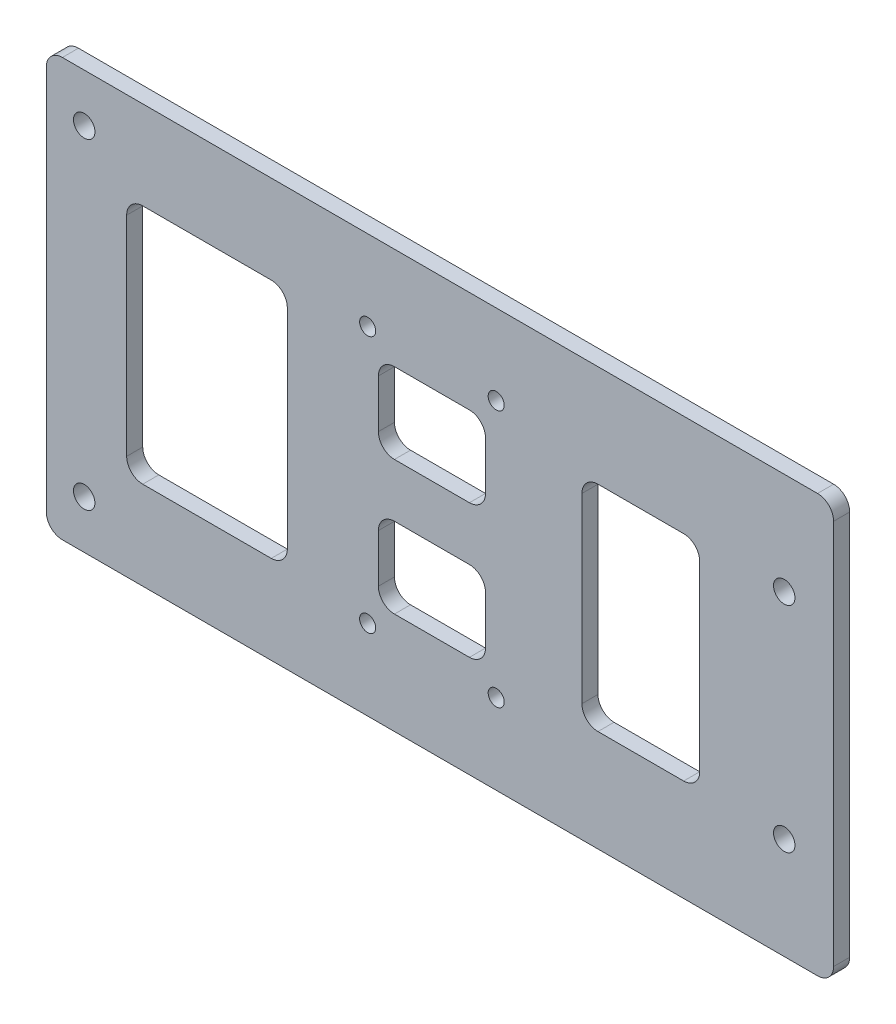
SolidWorks part; units mm, degrees
material "Caoba"
ref_plane "Alzado" through (0, 0, 0) normal (0, 0, 1) x (1, 0, 0)
ref_plane "Planta" through (0, 0, 0) normal (0, 1, 0) x (1, 0, 0)
ref_plane "Vista lateral" through (0, 0, 0) normal (1, 0, 0) x (0, 0, -1)
sketch "Croquis1" plane through (0, 0, 0) normal (0, 0, 1) x (1, 0, 0)
  circle A0 centre (0, 0) radius 100
  dimension "D1" = 200
extrude "Saliente-Extruir1" add sketch "Croquis1" along normal blind 3
sketch "Croquis3" plane through (0, 0, 3) normal (0, 0, 1) x (1, 0, 0)
  line L0 (0, 0) -> (190, 0) construction
  circle A0 centre (190, 0) radius 120
  dimension "D1" = 240
  dimension "D2" = 190
extrude "Cortar-Extruir1" cut sketch "Croquis3" against normal blind 3
sketch "Croquis5" plane through (0, 0, 3) normal (0, 0, 1) x (1, 0, 0)
  line L0 (0, -100) -> (0, 100) construction
  line L1 (-100, 0) -> (70, 0) construction
  line L2 (0, 0) -> (-70.7107, -70.7107) construction
  line L3 (-70.7107, -70.7107) -> (70.7107, 70.7107) construction
  line L4 (0, 0) -> (-70.7107, 70.7107) construction
  line L5 (-70.7107, 70.7107) -> (70.7107, -70.7107) construction
  line L6 (-70.7107, -70.7107) -> (-58.3363, -83.085) construction
  line L9 (-58.3363, -83.085) -> (-83.085, -58.3363)
  line L11 (-83.085, -58.3363) -> (-65.4074, -40.6586)
  line L12 (-65.4074, -40.6586) -> (-40.6586, -65.4074)
  line L13 (-40.6586, -65.4074) -> (-58.3363, -83.085)
  line L14 (-70.7107, 70.7107) -> (-83.085, 58.3363) construction
  line L15 (-83.085, 58.3363) -> (-100, 0) construction
  line L17 (-83.085, 58.3363) -> (-58.3363, 83.085)
  line L18 (-58.3363, 83.085) -> (-40.6586, 65.4074)
  line L19 (-40.6586, 65.4074) -> (-65.4074, 40.6586)
  line L20 (-65.4074, 40.6586) -> (-83.085, 58.3363)
  line L22 (70.7107, -70.7107) -> (58.3363, -83.085) construction
  line L23 (58.3363, -83.085) -> (0, -100) construction
  line L24 (58.3363, -83.085) -> (83.085, -58.3363)
  line L25 (83.085, -58.3363) -> (65.4074, -40.6586)
  line L26 (65.4074, -40.6586) -> (40.6586, -65.4074)
  line L27 (40.6586, -65.4074) -> (58.3363, -83.085)
  line L28 (70.7107, 70.7107) -> (58.3363, 83.085) construction
  line L29 (58.3363, 83.085) -> (0, 100) construction
  line L30 (58.3363, 83.085) -> (83.085, 58.3363)
  line L31 (83.085, 58.3363) -> (65.4074, 40.6586)
  line L32 (65.4074, 40.6586) -> (40.6586, 65.4074)
  line L33 (40.6586, 65.4074) -> (58.3363, 83.085)
  arc A0 (83.4211, 55.1446) -> (83.4211, -55.1446) centre (0, 0) ccw construction
  arc A1 (83.4211, 55.1446) -> (83.4211, -55.1446) centre (190, 0) ccw construction
  point P36 (0, 0)
  dimension "D2" = 17.5
  dimension "D3" = 25
  dimension "D4" = 35
  dimension "D5" = 25
  dimension "D6" = 35
  dimension "D8" = 25
  dimension "D9" = 17.5
  dimension "D7" = 35
  dimension "D10" = 90
  dimension "D11" = 17.5
  dimension "D12" = 17.5
  dimension "D13" = 35
  dimension "D14" = 25
  dimension "D15" = 134.3503
  dimension "D16" = 100
extrude "Cortar-Extruir6" cut sketch "Croquis5" against normal blind 10
sketch "Croquis12" plane through (0, 0, 3) normal (0, 0, 1) x (1, 0, 0)
  line L0 (-53.033, -53.033) -> (-39.9421, -50.0116) construction
  line L1 (-40.6586, -65.4074) -> (-65.4074, -40.6586) construction
  line L2 (-39.9421, -50.0116) -> (-36.8049, -63.6043) construction
  line L3 (-36.8049, -63.6043) -> (-63.6043, -36.8049) construction
  line L4 (-63.6043, -36.8049) -> (-47.6661, -20.8667) construction
  line L6 (53.033, -53.033) -> (-53.033, 53.033) construction
  line L7 (65.4074, -40.6586) -> (40.6586, -65.4074) construction
  line L8 (-65.4074, 40.6586) -> (-40.6586, 65.4074) construction
  line L9 (36.8049, 63.6043) -> (20.8667, 47.6661) construction
  line L10 (63.6043, 36.8049) -> (36.8049, 63.6043) construction
  line L11 (50.0116, 39.9421) -> (63.6043, 36.8049) construction
  line L12 (53.033, 53.033) -> (50.0116, 39.9421) construction
  line L14 (53.033, -53.033) -> (50.2046, -50.2046) construction
  line L15 (50.2046, -50.2046) -> (36.8049, -63.6043) construction
  line L16 (36.8049, -63.6043) -> (63.6043, -36.8049) construction
  line L17 (63.6043, -36.8049) -> (47.6661, -20.8667) construction
  line L19 (-53.033, -53.033) -> (53.033, 53.033) construction
  line L20 (-36.8049, 63.6043) -> (-20.8667, 47.6661) construction
  line L21 (-63.6043, 36.8049) -> (-36.8049, 63.6043) construction
  line L22 (-50.2046, 50.2046) -> (-63.6043, 36.8049) construction
  line L23 (-53.033, 53.033) -> (-50.2046, 50.2046) construction
  circle A0 centre (-63.6043, -36.8049) radius 1.5
  circle A1 centre (-36.8049, -63.6043) radius 1.5
  circle A2 centre (-47.6661, -20.8667) radius 1.5
  circle A3 centre (-20.8667, -47.6661) radius 1.5
  circle A5 centre (47.6661, 20.8667) radius 1.5
  circle A6 centre (20.8667, 47.6661) radius 1.5
  circle A7 centre (63.6043, 36.8049) radius 1.5
  circle A8 centre (36.8049, 63.6043) radius 1.5
  circle A10 centre (20.8667, -47.6661) radius 1.5
  circle A11 centre (47.6661, -20.8667) radius 1.5
  circle A12 centre (63.6043, -36.8049) radius 1.5
  circle A13 centre (36.8049, -63.6043) radius 1.5
  circle A15 centre (-63.6043, 36.8049) radius 1.5
  circle A16 centre (-36.8049, 63.6043) radius 1.5
  circle A17 centre (-20.8667, 47.6661) radius 1.5
  circle A18 centre (-47.6661, 20.8667) radius 1.5
  dimension "D2" = 3
  dimension "D3" = 3
  dimension "D4" = 4
  dimension "D5" = 4
  dimension "D6" = 3
  dimension "D7" = 3
  dimension "D8" = 37.9
  dimension "D9" = 22.54
  dimension "D10" = 22.54
  dimension "D11" = 37.9
  dimension "D12" = 18.95
  dimension "D13" = 18.95
  dimension "D14" = 3
  dimension "D15" = 3
  dimension "D16" = 3
  dimension "D17" = 3
  dimension "D18" = 37.9
  dimension "D19" = 22.54
  dimension "D20" = 22.54
  dimension "D21" = 37.9
  dimension "D22" = 4
  dimension "D1" = 13.95
extrude "Cortar-Extruir7" cut sketch "Croquis12" against normal through all
sketch "Croquis9" plane through (0, 0, 3) normal (0, 0, 1) x (1, 0, 0)
  line L0 (0, 0) -> (-100, 0) construction
  line L5 (0, 100) -> (0, -100) construction
  line L6 (20, 5) -> (29, 5)
  line L7 (20, 5) -> (20, -5)
  line L8 (20, -5) -> (29, -5)
  line L9 (29, 5) -> (29, -5)
  line L10 (-5, -49) -> (5, -49)
  line L11 (-49, 5) -> (-58, 5)
  line L12 (-49, 5) -> (-49, -5)
  line L13 (-49, -5) -> (-58, -5)
  line L14 (-58, 5) -> (-58, -5)
  line L15 (-5, 58) -> (5, 58)
  line L16 (-5, 58) -> (-5, 49)
  line L17 (-5, 49) -> (5, 49)
  line L18 (5, 58) -> (5, 49)
  line L19 (5, -58) -> (5, -49)
  line L20 (-5, -58) -> (5, -58)
  line L21 (-5, -58) -> (-5, -49)
  line L22 (0, 0) -> (70, 0) construction
  line L24 (-52.061, -4) -> (-52.0837, -4) construction
  arc A6 (-81.9939, 57.2451) -> (-81.9939, -57.2451) centre (0, 0) ccw construction
  arc A7 (83.4211, 55.1446) -> (83.4211, -55.1446) centre (190, 0) ccw construction
  dimension "D7" = 49
  dimension "D8" = 49
  dimension "D9" = 20
  dimension "D10" = 49
  dimension "D28" = 5
  dimension "D37" = 5
  dimension "D62" = 9
  dimension "D32" = 10
  dimension "D50" = 5
  dimension "D17" = 9
  dimension "D18" = 10
  dimension "D33" = 5
  dimension "D47" = 10
  dimension "D48" = 9
  dimension "D66" = 9
  dimension "D67" = 10
extrude "Cortar-Extruir5" cut sketch "Croquis9" against normal blind 10
sketch "Croquis13" plane through (0, 0, 3) normal (0, 0, 1) x (1, 0, 0)
  line L0 (0, 100) -> (0, -100) construction
  line L1 (-100, 0) -> (70, 0) construction
  line L2 (-70.7107, 70.7107) -> (70.7107, -70.7107) construction
  line L3 (-70.7093, -70.7093) -> (70.712, 70.712) construction
  line L4 (-70.7107, 70.7107) -> (-70.7093, -70.7093) construction
  line L5 (-70.7093, -70.7093) -> (70.7107, -70.7107) construction
  line L6 (70.7107, -70.7107) -> (70.712, 70.712) construction
  line L7 (70.712, 70.712) -> (-70.7107, 70.7107) construction
  line L9 (-37, 20) -> (8, 20)
  line L10 (-37, 20) -> (-37, -18)
  line L11 (-37, -18) -> (8, -18)
  line L12 (8, 20) -> (8, -18)
  arc A0 (57.2451, 81.9939) -> (-57.2451, 81.9939) centre (0, 0) ccw construction
  arc A1 (-57.2451, -81.9939) -> (57.2451, -81.9939) centre (0, 0) ccw construction
  arc A2 (-81.9939, 57.2451) -> (-81.9939, -57.2451) centre (0, 0) ccw construction
  arc A3 (83.4211, 55.1446) -> (83.4211, -55.1446) centre (190, 0) ccw construction
  circle A4 centre (-70.7103, 30) radius 2
  circle A5 centre (-70.7097, -30) radius 2
  circle A8 centre (0, -93.47) radius 1.5
  circle A9 centre (0, 93.47) radius 1.5
  circle A10 centre (60, -20) radius 2
  circle A11 centre (60, 20) radius 2
  point P37 (-15, 0)
  dimension "D9" = 4
  dimension "D10" = 4
  dimension "D11" = 30
  dimension "D12" = 30
  dimension "D13" = 4
  dimension "D14" = 4
  dimension "D15" = 60
  dimension "D16" = 60
  dimension "D17" = 3
  dimension "D18" = 93.47
  dimension "D19" = 93.47
  dimension "D20" = 3
  dimension "D25" = 20
  dimension "D26" = 20
  dimension "D1" = 45
  dimension "D2" = 200
  dimension "D3" = 0
  dimension "D4" = 200
  dimension "D5" = 45
  dimension "D6" = 0
  dimension "D7" = 141.42
  dimension "D8" = 141.42
  dimension "D21" = 45
  dimension "D22" = 38
  dimension "D23" = 18
  dimension "D24" = 37
extrude "Cortar-Extruir8" cut sketch "Croquis13" against normal through all
fillet "Redondeo2" radius 3 20 edges at (-81.9939, 57.2451, 1.5) (-65.4074, 40.6586, 1.5) (-40.6586, 65.4074, 1.5) (-57.2451, 81.9939, 1.5) (65.4074, 40.6586, 1.5) (40.6586, 65.4074, 1.5) (57.2451, 81.9939, 1.5) (81.9939, 57.2451, 1.5) (65.4074, -40.6586, 1.5) (40.6586, -65.4074, 1.5) (81.9939, -57.2451, 1.5) (57.2451, -81.9939, 1.5) (-65.4074, -40.6586, 1.5) (-81.9939, -57.2451, 1.5) (-57.2451, -81.9939, 1.5) (-40.6586, -65.4074, 1.5) (8, -18, 1.5) (8, 20, 1.5) (-37, -18, 1.5) (-37, 20, 1.5)
fillet "Redondeo3" radius 3 2 edges at (83.4211, -55.1446, 1.5) (83.4211, 55.1446, 1.5)
sketch "Croquis14" plane through (0, 0, 3) normal (0, 0, 1) x (1, 0, 0)
  line L0 (42.78, -67.5287) -> (54.6657, -79.4145) construction
  line L1 (0, 0) -> (75.1866, -75.1866) construction
  line L2 (0, 100) -> (0, -100) construction
  line L7 (-100, 0) -> (83.579, 0) construction
  line L8 (0, 0) -> (88.3883, 88.3883) construction
  line L9 (0, 0) -> (-88.3883, -88.3883) construction
  line L10 (0, 0) -> (-74.4604, 74.4604) construction
  circle A0 centre (38.8032, -75) radius 1.5
  circle A1 centre (-75, -38.8032) radius 1.5
  circle A2 centre (-38.7968, -75) radius 1.5
  circle A8 centre (-75, 38.7968) radius 1.5
  circle A9 centre (-38.8032, 75) radius 1.5
  circle A10 centre (38.7968, 75) radius 1.5
  arc A12 (54.1695, 84.0575) -> (-54.1695, 84.0575) centre (0, 0) ccw construction
  arc A13 (-54.1695, -84.0575) -> (54.1695, -84.0575) centre (0, 0) ccw construction
  arc A14 (-84.0575, 54.1695) -> (-84.0575, -54.1695) centre (0, 0) ccw construction
  circle A26 centre (75, 38.8032) radius 1.5 [skipped]
  circle A27 centre (75, -38.7968) radius 1.5 [skipped]
  point P23 (-5.3984, -2.1885)
  point P24 (0, 0)
  dimension "D1" = 3
  dimension "D2" = 8.095
  dimension "D3" = 75
  dimension "D4" = 3
  dimension "D5" = 75
  dimension "D7" = 4
  dimension "D8" = 38.7968
  dimension "D9" = 75
  dimension "D24" = 77.6
  dimension "D6" = 125
  dimension "D19" = 125
  dimension "D20" = 45
  dimension "D21" = 45
  dimension "D22" = 45
  dimension "D23" = 45
extrude "Cortar-Extruir9" cut sketch "Croquis14" against normal through all
sketch "Croquis15" plane through (0, 0, 0) normal (0, 0, -1) x (-1, 0, 0)
  line L0 (0, 100) -> (0, -100) construction
  line L1 (-70, 0) -> (100, 0) construction
  circle A0 centre (16.19, 41.3081) radius 1.5
  circle A1 centre (16.19, -41.3181) radius 1.5
  arc A2 (54.1695, 84.0575) -> (-54.1695, 84.0575) centre (0, 0) ccw construction
  arc A3 (-54.1695, -84.0575) -> (54.1695, -84.0575) centre (0, 0) ccw construction
  arc A4 (-79.3447, -46.4262) -> (-79.3447, 46.4262) centre (-190, 0) ccw construction
  arc A5 (84.0575, -54.1695) -> (84.0575, 54.1695) centre (0, 0) ccw construction
  circle A6 centre (-16.705, -10.3179) radius 1.5
  dimension "D1" = 3
  dimension "D2" = 3
  dimension "D3" = 82.6262
  dimension "D4" = 16.19
  dimension "D5" = 41.3182
  dimension "D6" = 41.3081
  dimension "D7" = 3
  dimension "D8" = 51.626
  dimension "D9" = 32.895
extrude "Cortar-Extruir10" cut sketch "Croquis15" against normal blind 10
sketch "Croquis16" plane through (0, 0, 0) normal (0, 0, -1) x (-1, 0, 0)
  line L0 (-115, 0) -> (100, 0) construction
  line L1 (-115, 105) -> (100, 105)
  line L2 (-115, 105) -> (-115, 39)
  line L3 (-115, 39) -> (100, 39)
  line L4 (100, 105) -> (100, 39)
  line L5 (-115, -39) -> (100, -39)
  line L6 (100, -105) -> (100, -39)
  line L7 (-115, -105) -> (100, -105)
  line L8 (-115, -105) -> (-115, -39)
  line L9 (0, 100) -> (0, -100) construction
  arc A0 (84.0575, -54.1695) -> (84.0575, 54.1695) centre (0, 0) ccw construction
  arc A1 (54.1695, 84.0575) -> (-54.1695, 84.0575) centre (0, 0) ccw construction
  arc A2 (-54.1695, -84.0575) -> (54.1695, -84.0575) centre (0, 0) ccw construction
  dimension "D1" = 215
  dimension "D2" = 215
  dimension "D3" = 66
  dimension "D4" = 39
  dimension "D5" = 115
extrude "Cortar-Extruir11" cut sketch "Croquis16" against normal blind 10
sketch "Croquis17" plane through (0, 0, 0) normal (0, 0, -1) x (-1, 0, 0)
  line L5 (-76.5143, -39) -> (73.513, -39) construction
  line L6 (80, -34) -> (-70, -34)
  line L7 (80, -34) -> (80, -39)
  line L8 (80, -39) -> (-70, -39)
  line L9 (-70, -34) -> (-70, -39)
  line L10 (100, 0) -> (-70, 0) construction
  line L11 (80, 39) -> (-70, 39)
  line L12 (-70, 34) -> (-70, 39)
  line L13 (80, 34) -> (-70, 34)
  line L14 (80, 34) -> (80, 39)
  line L16 (87, 25) -> (-53, 25)
  line L17 (87, 25) -> (87, -25)
  line L18 (87, -25) -> (-53, -25)
  line L19 (-53, 25) -> (-53, -25)
  arc A0 (-76.5143, -39) -> (-76.5143, 39) centre (-190, 0) ccw construction
  arc A1 (92.0815, -39) -> (92.0815, 39) centre (0, 0) ccw construction
  dimension "D1" = 150
  dimension "D2" = 5
  dimension "D3" = 270
  dimension "D4" = 140
  dimension "D5" = 50
  dimension "D6" = 87
  dimension "D7" = 14
extrude "Saliente-Extruir3" add sketch "Croquis17" against normal blind 3
sketch "Croquis18" plane through (0, 0, 3) normal (0, 0, 1) x (1, 0, 0)
  line L0 (-92.0815, 39) -> (76.5143, 39) construction
  line L1 (70, 0) -> (-100, 0) construction
  line L2 (-7.7836, 39) -> (-7.7836, -39) construction
  line L3 (76.5143, -39) -> (-92.0815, -39) construction
  line L4 (-15.7836, -5) -> (4.2164, -5)
  line L5 (-15.7836, 20) -> (4.2164, 20)
  line L6 (-15.7836, 20) -> (-15.7836, 5)
  line L7 (-15.7836, 5) -> (4.2164, 5)
  line L8 (4.2164, 20) -> (4.2164, 5)
  line L9 (4.2164, -20) -> (4.2164, -5)
  line L10 (-15.7836, -20) -> (4.2164, -20)
  line L11 (-15.7836, -20) -> (-15.7836, -5)
  line L13 (-62.7836, 22.5) -> (-32.7836, 22.5)
  line L14 (-62.7836, 22.5) -> (-62.7836, -22.5)
  line L15 (-62.7836, -22.5) -> (-32.7836, -22.5)
  line L16 (-32.7836, 22.5) -> (-32.7836, -22.5)
  line L17 (-112.7836, 39) -> (-77.7836, 39)
  line L18 (-112.7836, 39) -> (-112.7836, -39)
  line L19 (-112.7836, -39) -> (-77.7836, -39)
  line L20 (-77.7836, 39) -> (-77.7836, -39)
  line L21 (22.2164, 20) -> (44.2164, 20)
  line L22 (22.2164, 20) -> (22.2164, -20)
  line L23 (22.2164, -20) -> (44.2164, -20)
  line L24 (44.2164, 20) -> (44.2164, -20)
  line L25 (69.2164, 39) -> (89.2164, 39)
  line L26 (69.2164, 39) -> (69.2164, -39)
  line L27 (69.2164, -39) -> (89.2164, -39)
  line L28 (89.2164, 39) -> (89.2164, -39)
  circle A0 centre (-17.7836, 24) radius 1.5
  circle A1 centre (6.2164, 24) radius 1.5
  circle A2 centre (-17.7836, -24) radius 1.5
  circle A3 centre (6.2164, -24) radius 1.5
  arc A4 (76.5143, 39) -> (76.5143, -39) centre (190, 0) ccw construction
  arc A5 (-92.0815, 39) -> (-92.0815, -39) centre (0, 0) ccw construction
  dimension "D1" = 48
  dimension "D2" = 24
  dimension "D3" = 48
  dimension "D4" = 24
  dimension "D5" = 3
  dimension "D6" = 3
  dimension "D7" = 3
  dimension "D8" = 3
  dimension "D9" = 15
  dimension "D10" = 10
  dimension "D11" = 10
  dimension "D12" = 15
  dimension "D13" = 15
  dimension "D14" = 20
  dimension "D15" = 8
  dimension "D16" = 19
  dimension "D17" = 45
  dimension "D18" = 16.5
  dimension "D19" = 25
  dimension "D20" = 30
  dimension "D21" = 78
  dimension "D22" = 35
  dimension "D23" = 70
  dimension "D24" = 40
  dimension "D25" = 22
  dimension "D26" = 30
  dimension "D27" = 19
  dimension "D28" = 20
  dimension "D29" = 77
  dimension "D30" = 78
extrude "Cortar-Extruir12" cut sketch "Croquis18" against normal blind 3
fillet "Redondeo4" radius 3 20 edges at (-32.7836, -22.5, 1.5) (-32.7836, 22.5, 1.5) (-62.7836, -22.5, 1.5) (-62.7836, 22.5, 1.5) (4.2164, 5, 1.5) (4.2164, 20, 1.5) (-15.7836, 20, 1.5) (-15.7836, 5, 1.5) (4.2164, -20, 1.5) (4.2164, -5, 1.5) (-15.7836, -20, 1.5) (-15.7836, -5, 1.5) (44.2164, -20, 1.5) (22.2164, -20, 1.5) (44.2164, 20, 1.5) (22.2164, 20, 1.5) (-77.7836, -39, 1.5) (-77.7836, 39, 1.5) (69.2164, 39, 1.5) (69.2164, -39, 1.5)
